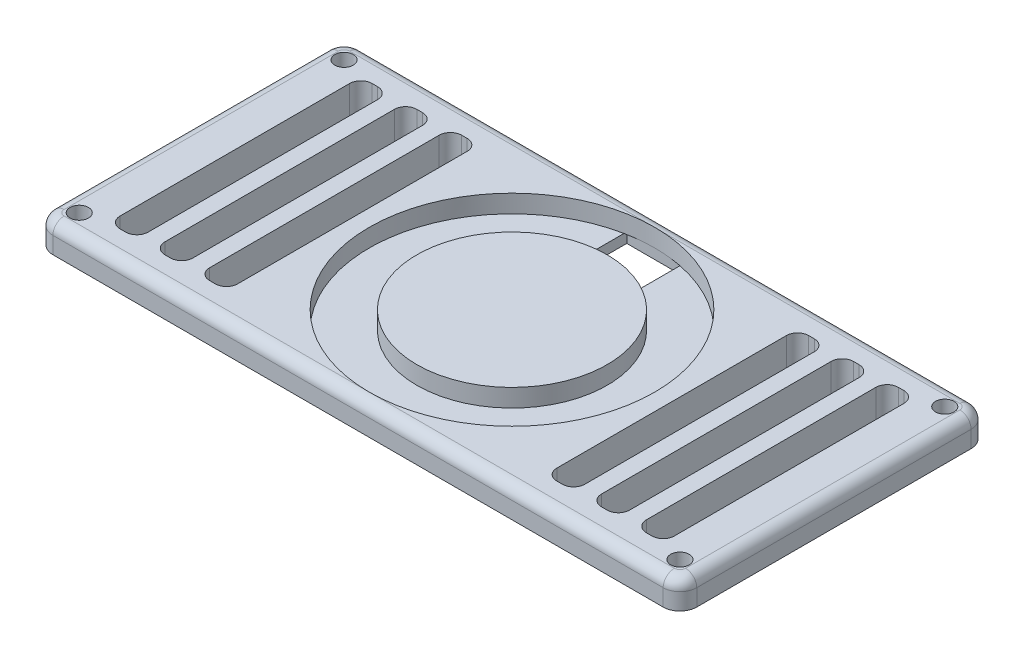
SolidWorks part; units mm, degrees
ref_plane "Спереди" through (0, 0, 0) normal (0, 0, 1) x (1, 0, 0)
ref_plane "Сверху" through (0, 0, 0) normal (0, 1, 0) x (1, 0, 0)
ref_plane "Справа" through (0, 0, 0) normal (1, 0, 0) x (0, 0, -1)
sketch "Эскиз1" plane through (0, 0, 0) normal (0, 1, 0) x (1, 0, 0)
  line L1 (-52.4047, 37.4765) -> (56.5953, 37.4765)
  line L2 (-55.4047, 34.4765) -> (-55.4047, -14.5235)
  line L3 (-52.4047, -17.5235) -> (56.5953, -17.5235)
  line L4 (59.5953, 34.4765) -> (59.5953, -14.5235)
  arc A0 (-55.4047, -14.5235) -> (-52.4047, -17.5235) centre (-52.4047, -14.5235) ccw
  arc A1 (56.5953, -17.5235) -> (59.5953, -14.5235) centre (56.5953, -14.5235) ccw
  arc A2 (56.5953, 37.4765) -> (59.5953, 34.4765) centre (56.5953, 34.4765) cw
  arc A3 (-52.4047, 37.4765) -> (-55.4047, 34.4765) centre (-52.4047, 34.4765) ccw
  dimension "D3" = 3
  dimension "D1" = 115
  dimension "D2" = 55
extrude "Бобышка-Вытянуть1" add sketch "Эскиз1" along normal blind 5
sketch "Эскиз2" plane through (0, 5, 0) normal (0, 1, 0) x (1, 0, 0)
  line L0 (-55.4047, 34.4765) -> (-55.4047, -14.5235) construction
  circle A0 centre (2.0953, 9.9765) radius 25.5
  circle A1 centre (2.0953, 9.9765) radius 17
  dimension "D1" = 51
  dimension "D2" = 34
  dimension "D3" = 57.5
extrude "Вырез-Вытянуть1" cut sketch "Эскиз2" against normal blind 3.2
sketch "Эскиз3" plane through (0, 5, 0) normal (0, 1, 0) x (1, 0, 0)
  line L0 (59.5953, -14.5235) -> (59.5953, 34.4765) construction
  line L1 (-45.4047, 32.4765) -> (-44.4047, 32.4765)
  line L2 (-47.4047, 30.4765) -> (-47.4047, -10.5235)
  line L3 (-45.4047, -12.5235) -> (-44.4047, -12.5235)
  line L4 (-42.4047, 30.4765) -> (-42.4047, -10.5235)
  line L5 (-37.4047, 32.4765) -> (-36.4047, 32.4765)
  line L6 (-39.4047, 30.4765) -> (-39.4047, -10.5235)
  line L7 (-37.4047, -12.5235) -> (-36.4047, -12.5235)
  line L8 (-34.4047, 30.4765) -> (-34.4047, -10.5235)
  line L9 (-29.4047, 32.4765) -> (-28.4047, 32.4765)
  line L10 (-31.4047, 30.4765) -> (-31.4047, -10.5235)
  line L11 (-29.4047, -12.5235) -> (-28.4047, -12.5235)
  line L12 (-26.4047, 30.4765) -> (-26.4047, -10.5235)
  line L13 (49.5953, 32.4765) -> (48.5953, 32.4765)
  line L14 (51.5953, 30.4765) -> (51.5953, -10.5235)
  line L15 (49.5953, -12.5235) -> (48.5953, -12.5235)
  line L16 (46.5953, 30.4765) -> (46.5953, -10.5235)
  line L17 (41.5953, 32.4765) -> (40.5953, 32.4765)
  line L18 (43.5953, 30.4765) -> (43.5953, -10.5235)
  line L19 (41.5953, -12.5235) -> (40.5953, -12.5235)
  line L20 (38.5953, 30.4765) -> (38.5953, -10.5235)
  line L21 (33.5953, 32.4765) -> (32.5953, 32.4765)
  line L22 (35.5953, 30.4765) -> (35.5953, -10.5235)
  line L23 (33.5953, -12.5235) -> (32.5953, -12.5235)
  line L24 (30.5953, 30.4765) -> (30.5953, -10.5235)
  line L25 (-55.4047, 34.4765) -> (-55.4047, -14.5235) construction
  line L26 (-52.4047, -17.5235) -> (56.5953, -17.5235) construction
  arc A0 (-28.4047, 32.4765) -> (-26.4047, 30.4765) centre (-28.4047, 30.4765) cw
  arc A1 (-29.4047, 32.4765) -> (-31.4047, 30.4765) centre (-29.4047, 30.4765) ccw
  arc A2 (-36.4047, 32.4765) -> (-34.4047, 30.4765) centre (-36.4047, 30.4765) cw
  arc A3 (-37.4047, 32.4765) -> (-39.4047, 30.4765) centre (-37.4047, 30.4765) ccw
  arc A4 (-44.4047, 32.4765) -> (-42.4047, 30.4765) centre (-44.4047, 30.4765) cw
  arc A5 (-45.4047, 32.4765) -> (-47.4047, 30.4765) centre (-45.4047, 30.4765) ccw
  arc A6 (-28.4047, -12.5235) -> (-26.4047, -10.5235) centre (-28.4047, -10.5235) ccw
  arc A7 (-31.4047, -10.5235) -> (-29.4047, -12.5235) centre (-29.4047, -10.5235) ccw
  arc A8 (-36.4047, -12.5235) -> (-34.4047, -10.5235) centre (-36.4047, -10.5235) ccw
  arc A9 (-39.4047, -10.5235) -> (-37.4047, -12.5235) centre (-37.4047, -10.5235) ccw
  arc A10 (-44.4047, -12.5235) -> (-42.4047, -10.5235) centre (-44.4047, -10.5235) ccw
  arc A11 (-47.4047, -10.5235) -> (-45.4047, -12.5235) centre (-45.4047, -10.5235) ccw
  arc A12 (51.5953, -10.5235) -> (49.5953, -12.5235) centre (49.5953, -10.5235) cw
  arc A13 (48.5953, -12.5235) -> (46.5953, -10.5235) centre (48.5953, -10.5235) cw
  arc A14 (43.5953, -10.5235) -> (41.5953, -12.5235) centre (41.5953, -10.5235) cw
  arc A15 (40.5953, -12.5235) -> (38.5953, -10.5235) centre (40.5953, -10.5235) cw
  arc A16 (35.5953, -10.5235) -> (33.5953, -12.5235) centre (33.5953, -10.5235) cw
  arc A17 (32.5953, -12.5235) -> (30.5953, -10.5235) centre (32.5953, -10.5235) cw
  arc A18 (51.5953, 30.4765) -> (49.5953, 32.4765) centre (49.5953, 30.4765) ccw
  arc A19 (48.5953, 32.4765) -> (46.5953, 30.4765) centre (48.5953, 30.4765) ccw
  arc A20 (41.5953, 32.4765) -> (43.5953, 30.4765) centre (41.5953, 30.4765) cw
  arc A21 (40.5953, 32.4765) -> (38.5953, 30.4765) centre (40.5953, 30.4765) ccw
  arc A22 (33.5953, 32.4765) -> (35.5953, 30.4765) centre (33.5953, 30.4765) cw
  arc A23 (32.5953, 32.4765) -> (30.5953, 30.4765) centre (32.5953, 30.4765) ccw
  point P24 (35.5953, 9.9765)
  point P29 (-44.9047, -12.5235)
  point P30 (41.0953, 32.4765)
  dimension "D25" = 2
  dimension "D26" = 2
  dimension "D27" = 2
  dimension "D1" = 5
  dimension "D2" = 5
  dimension "D3" = 5
  dimension "D4" = 3
  dimension "D5" = 3
  dimension "D6" = 3
  dimension "D7" = 3
  dimension "D8" = 5
  dimension "D9" = 5
  dimension "D10" = 5
  dimension "D11" = 8
  dimension "D12" = 8
  dimension "D13" = 45
  dimension "D14" = 45
  dimension "D15" = 45
  dimension "D16" = 45
  dimension "D17" = 45
  dimension "D18" = 45
  dimension "D19" = 5
  dimension "D20" = 5
  dimension "D21" = 5
  dimension "D22" = 5
  dimension "D23" = 5
  dimension "D24" = 5
extrude "Вырез-Вытянуть2" cut sketch "Эскиз3" against normal blind 18.2
fillet "Скругление1" radius 2 8 edges at (-54.5261, 5, 16.6448) (-55.4047, 5, -9.9765) (-54.5261, 5, -36.5978) (2.0953, 5, -37.4765) (58.7166, 5, -36.5978) (59.5953, 5, -9.9765) (58.7166, 5, 16.6448) (2.0953, 5, 17.5235)
sketch "Эскиз4" plane through (0, 0, 0) normal (0, -1, 0) x (1, 0, 0)
  line L1 (-52.4047, 14.5235) -> (-50.7047, 14.5235)
  line L2 (-52.4047, 14.5235) -> (-52.4047, 12.8235)
  line L3 (-52.4047, 12.8235) -> (-50.7047, 12.8235)
  line L4 (-50.7047, 14.5235) -> (-50.7047, 12.8235)
  line L5 (-52.4047, -32.7765) -> (-50.7047, -32.7765)
  line L6 (-52.4047, -32.7765) -> (-52.4047, -34.4765)
  line L7 (-52.4047, -34.4765) -> (-50.7047, -34.4765)
  line L8 (-50.7047, -32.7765) -> (-50.7047, -34.4765)
  line L9 (54.8953, -32.7765) -> (56.5953, -32.7765)
  line L10 (54.8953, -32.7765) -> (54.8953, -34.4765)
  line L11 (54.8953, -34.4765) -> (56.5953, -34.4765)
  line L12 (56.5953, -32.7765) -> (56.5953, -34.4765)
  line L13 (54.8953, 14.5235) -> (56.5953, 14.5235)
  line L14 (54.8953, 14.5235) -> (54.8953, 12.8235)
  line L15 (54.8953, 12.8235) -> (56.5953, 12.8235)
  line L16 (56.5953, 14.5235) -> (56.5953, 12.8235)
extrude "Вырез-Вытянуть3" cut sketch "Эскиз4" against normal blind 71
sketch "Эскиз5" plane through (0, 5, 0) normal (0, 1, 0) x (1, 0, 0)
  circle A0 centre (-51.5547, 33.6265) radius 1.65
  circle A1 centre (-51.5547, -13.6735) radius 1.65
  circle A2 centre (55.7453, 33.6265) radius 1.65
  circle A3 centre (55.7453, -13.6735) radius 1.65
  dimension "D1" = 3.3
  dimension "D2" = 3.3
  dimension "D3" = 3.3
  dimension "D4" = 3.3
extrude "Вырез-Вытянуть4" cut sketch "Эскиз5" against normal blind 3
sketch "Эскиз6" plane through (0, 1.8, 0) normal (0, 1, 0) x (1, 0, 0)
  line L0 (-55.4047, -14.5235) -> (-55.4047, 34.4765) construction
  line L1 (-2.9047, 35.4765) -> (7.0953, 35.4765)
  line L2 (-2.9047, 35.4765) -> (-2.9047, 27.6765)
  line L3 (-2.9047, 27.6765) -> (7.0953, 27.6765)
  line L4 (7.0953, 35.4765) -> (7.0953, 27.6765)
  line L6 (-52.4047, 37.4765) -> (56.5953, 37.4765) construction
  dimension "D1" = 10
  dimension "D2" = 7.8
  dimension "D3" = 52.5
  dimension "D4" = 2
extrude "Вырез-Вытянуть5" cut sketch "Эскиз6" against normal blind 9.4
